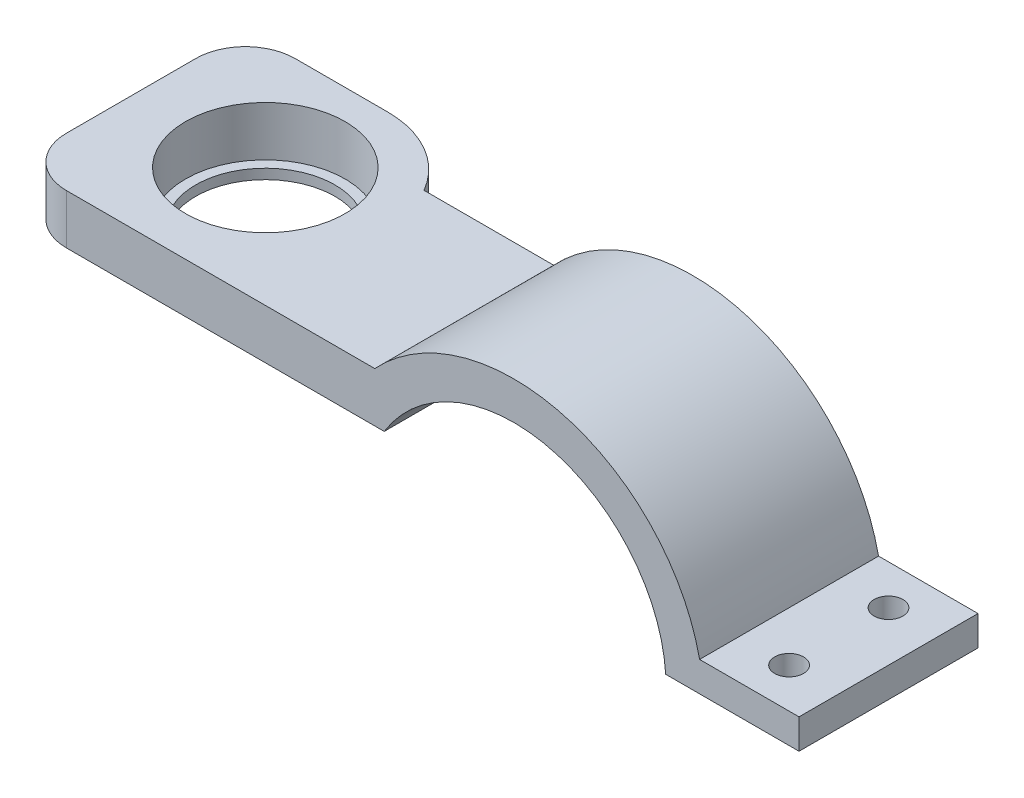
SolidWorks part; units mm, degrees
ref_plane "Front Plane" through (0, 0, 0) normal (0, 0, 1) x (1, 0, 0)
ref_plane "Top Plane" through (0, 0, 0) normal (0, 1, 0) x (1, 0, 0)
ref_plane "Right Plane" through (0, 0, 0) normal (1, 0, 0) x (0, 0, -1)
sketch "Sketch1" plane through (0, 0, 0) normal (0, 0, 1) x (1, 0, 0)
  line L0 (15.2673, 1) -> (28.6765, 1)
  line L1 (18.6765, 4) -> (28.6765, 4)
  line L2 (28.6765, 4) -> (28.6765, 1)
  line L3 (0, 0) -> (-50, 0) construction
  line L4 (-13.0419, 8) -> (-50, 8)
  line L5 (-50, 8) -> (-50, 13)
  line L6 (-50, 13) -> (-13.9932, 13)
  line L7 (0, 0) -> (28.6765, 0) construction
  arc A0 (15.2673, 1) -> (-13.0419, 8) centre (0, 0) ccw
  arc A1 (18.6765, 4) -> (-13.9932, 13) centre (0, 0) ccw
  dimension "D1" = 15.3
  dimension "D4" = 19.1
  dimension "D2" = 3
  dimension "D3" = 10
  dimension "D5" = 5
  dimension "D6" = 8
  dimension "D7" = 50
  dimension "D8" = 1
extrude "Boss-Extrude1" add sketch "Sketch1" along normal blind 18
sketch "Sketch3" plane through (0, 4, 0) normal (0, 1, 0) x (1, 0, 0)
  line L0 (28.6765, -18) -> (18.6765, -18) construction
  line L1 (23.6765, -14) -> (23.6765, -18) construction
  line L2 (23.6765, -4) -> (23.6765, 0) construction
  line L3 (28.6765, 0) -> (18.6765, 0) construction
  circle A0 centre (23.6765, -4) radius 1.45
  circle A1 centre (23.6765, -14) radius 1.45
  point P6 (23.6765, -18)
  dimension "D1" = 2.9
  dimension "D2" = 10
extrude "Cut-Extrude1" cut sketch "Sketch3" against normal through all
sketch "Sketch5" plane through (0, 8, 0) normal (0, -1, 0) x (1, 0, 0)
  line L7 (-13.0419, 18) -> (-13.0419, 0) construction
  line L8 (-50, 0) -> (-27.0419, 0)
  line L9 (-50, 0) -> (-50, -5)
  line L10 (-50, -5) -> (-27.0419, -5)
  line L11 (-27.0419, 0) -> (-27.0419, -5)
  dimension "D1" = 5
  dimension "D2" = 14
extrude "Boss-Extrude2" add sketch "Sketch5" against normal up to surface (5 mm away) up to face at (-31.9966, 13, 9)
sketch "Sketch6" plane through (0, 13, 0) normal (0, 1, 0) x (1, 0, 0)
  line L1 (-50, -18) -> (-50, 5) construction
  line L2 (-13.9932, -18) -> (-50, -18) construction
  circle A0 centre (-37, -6) radius 8.025
  dimension "D1" = 16.05
  dimension "D2" = 12
  dimension "D3" = 13
extrude "Cut-Extrude2" cut sketch "Sketch6" against normal through all
sketch "Sketch7" plane through (0, 8, 0) normal (0, -1, 0) x (1, 0, 0)
  circle A0 centre (-37, 6) radius 9
  circle A1 centre (-37, 6) radius 7
  dimension "D1" = 18
  dimension "D2" = 14
extrude "Boss-Extrude3" add sketch "Sketch7" along normal blind 1
fillet "Fillet1" radius 5 2 edges at (-50, 10.5, -5) (-50, 10.5, 18)
fillet "Fillet2" radius 10 1 edges at (-27.0419, 10.5, -5)
